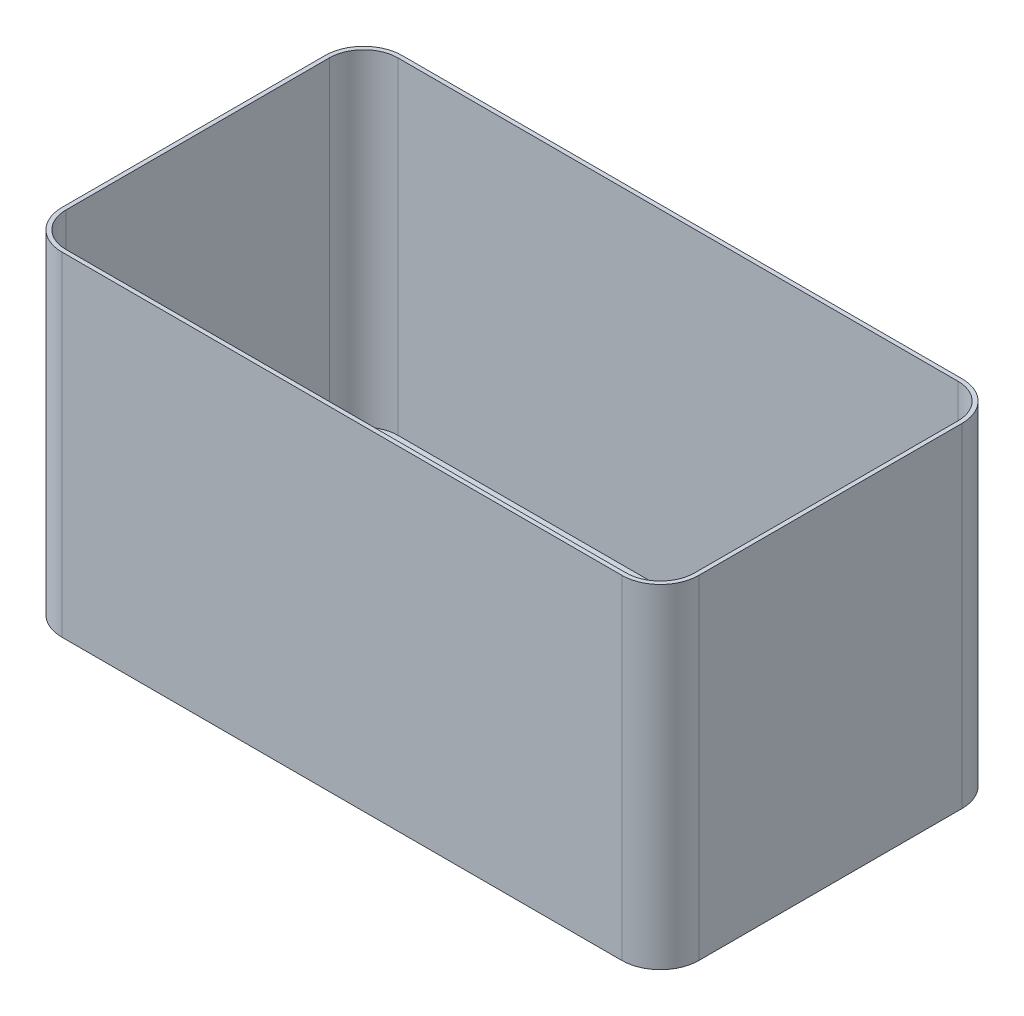
SolidWorks part; units mm, degrees
ref_plane "前视基准面" through (0, 0, 0) normal (0, 0, 1) x (1, 0, 0)
ref_plane "上视基准面" through (0, 0, 0) normal (0, 1, 0) x (1, 0, 0)
ref_plane "右视基准面" through (0, 0, 0) normal (1, 0, 0) x (0, 0, -1)
other "Configuration Table"
sketch "草图1" plane through (0, 0, 0) normal (0, 1, 0) x (1, 0, 0)
  line L1 (-167, 101.5) -> (167, 101.5)
  line L2 (-190, 78.5) -> (-190, -78.5)
  line L3 (-167, -101.5) -> (167, -101.5)
  line L4 (190, 78.5) -> (190, -78.5)
  line L5 (-190, 101.5) -> (190, -101.5) construction
  line L6 (-190, -101.5) -> (190, 101.5) construction
  arc A0 (167, -101.5) -> (190, -78.5) centre (167, -78.5) ccw
  arc A1 (167, 101.5) -> (190, 78.5) centre (167, 78.5) cw
  arc A2 (-190, -78.5) -> (-167, -101.5) centre (-167, -78.5) ccw
  arc A3 (-167, 101.5) -> (-190, 78.5) centre (-167, 78.5) ccw
  point P0 (0, 0)
  dimension "D3" = 23
  dimension "D1" = 380
  dimension "D2" = 203
extrude "凸台-拉伸1" add sketch "草图1" along normal blind 199
sketch "草图3" plane through (0, 199, 0) normal (0, 1, 0) x (1, 0, 0)
  line L0 (-190, 78.5) -> (-190, -78.5) construction
  line L1 (-167, 99) -> (167, 99)
  line L2 (-187.5, 78.5) -> (-187.5, -78.5)
  line L3 (-167, -99) -> (167, -99)
  line L4 (187.5, 78.5) -> (187.5, -78.5)
  line L5 (-187.5, 99) -> (187.5, -99) construction
  line L6 (-187.5, -99) -> (187.5, 99) construction
  line L7 (190, -78.5) -> (190, 78.5) construction
  arc A0 (-187.5, -78.5) -> (-167, -99) centre (-167, -78.5) ccw
  arc A1 (167, -99) -> (187.5, -78.5) centre (167, -78.5) ccw
  arc A2 (167, 99) -> (187.5, 78.5) centre (167, 78.5) cw
  arc A3 (-167, 99) -> (-187.5, 78.5) centre (-167, 78.5) ccw
  point P0 (0, 0)
  dimension "D5" = 20.5
  dimension "D1" = 198
  dimension "D2" = 375
  dimension "D3" = 2.5
  dimension "D4" = 2.5
extrude "切除-拉伸1" cut sketch "草图3" against normal blind 195
